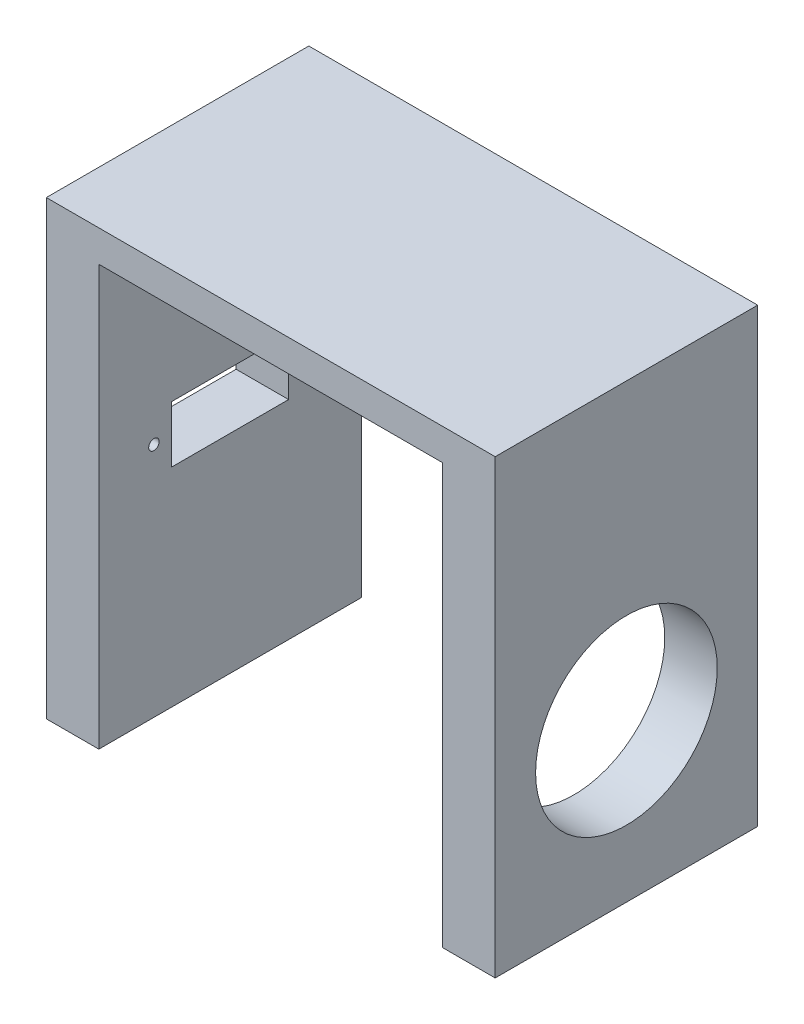
SolidWorks part; units mm, degrees
ref_plane "Front Plane" through (0, 0, 0) normal (0, 0, 1) x (1, 0, 0)
ref_plane "Top Plane" through (0, 0, 0) normal (0, 1, 0) x (1, 0, 0)
ref_plane "Right Plane" through (0, 0, 0) normal (1, 0, 0) x (0, 0, -1)
sketch "Sketch1" plane through (0, 0, 0) normal (0, 1, 0) x (1, 0, 0)
  line L1 (0, 0) -> (85.5, 0)
  line L2 (0, 0) -> (0, 50)
  line L3 (0, 50) -> (85.5, 50)
  line L4 (85.5, 0) -> (85.5, 50)
  dimension "D1" = 85.5
  dimension "D2" = 50
extrude "UAV Interface Top" add sketch "Sketch1" against normal blind 6
sketch "Sketch2" plane through (0, -6, 0) normal (0, -1, 0) x (1, 0, 0)
  line L0 (85.5, -50) -> (0, -50) construction
  line L1 (85.5, 0) -> (75.5, 0)
  line L2 (85.5, 0) -> (85.5, -50)
  line L3 (85.5, -50) -> (75.5, -50)
  line L4 (75.5, 0) -> (75.5, -50)
  dimension "D1" = 10
extrude "Spool and Motor Inserts" add sketch "Sketch2" along normal blind 80
ref_plane "Mirror Plane" through (42.75, 0, 0) normal (1, 0, 0) x (0, 0, -1)
mirror "Mirror1" about plane through (42.75, 0, 0) normal (1, 0, 0) of bodies 102 103
sketch "Sketch3" plane through (85.5, 0, 0) normal (1, 0, 0) x (0, 0, -1)
  line L0 (50, -86) -> (0, -86) construction
  circle A0 centre (25, -56) radius 17.3
  point P6 (25, -86)
  dimension "D1" = 34.6
  dimension "D2" = 30
extrude "Motor Cutout" cut sketch "Sketch3" against normal blind 30 contours A0
sketch "Sketch5" plane through (10, 0, 0) normal (1, 0, 0) x (0, 0, -1)
  line L0 (0, -86) -> (50, -86) construction
  line L1 (13.85, -35.6) -> (36.15, -35.6)
  line L2 (13.85, -35.6) -> (13.85, -46.4)
  line L3 (13.85, -46.4) -> (36.15, -46.4)
  line L4 (36.15, -35.6) -> (36.15, -46.4)
  line L5 (13.85, -35.6) -> (36.15, -46.4) construction
  line L6 (13.85, -46.4) -> (36.15, -35.6) construction
  line L7 (0, -6) -> (50, -6) construction
  line L8 (10.5, -41) -> (39.5, -41) construction
  circle A0 centre (10.5, -41) radius 1
  circle A1 centre (39.5, -41) radius 1
  point P0 (25, -41)
  point P8 (25, -86)
  point P13 (25, -41)
  dimension "D5" = 2
  dimension "D1" = 22.3
  dimension "D2" = 10.8
  dimension "D3" = 35
  dimension "D4" = 29
extrude "Servo Motor Cutout" cut sketch "Sketch5" against normal up to surface (10 mm away) contours L2 L1 L4 L3 up to face at (0, -43, -25)
extrude "Screw Cutouts" cut sketch "Sketch5<4>" against normal blind 2 contours A0 | A1
sketch "Sketch5<4>" plane through (10, 0, 0) normal (1, 0, 0) x (0, 0, -1) same geometry as "Sketch5"
